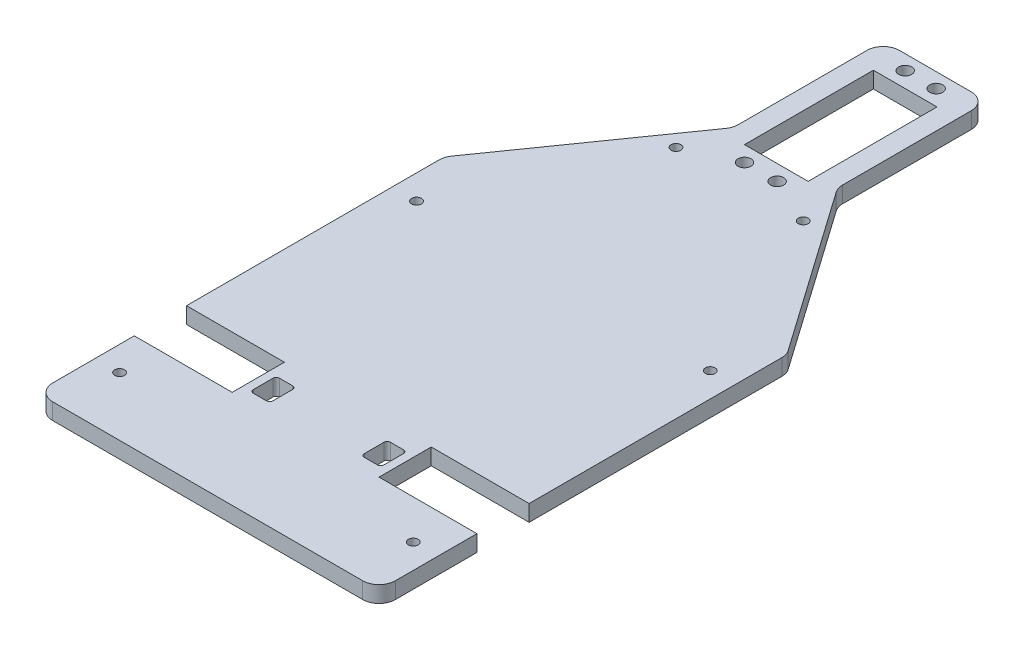
SolidWorks part; units mm, degrees
ref_plane "Front Plane" through (0, 0, 0) normal (0, 0, 1) x (1, 0, 0)
ref_plane "Top Plane" through (0, 0, 0) normal (0, 1, 0) x (1, 0, 0)
ref_plane "Right Plane" through (0, 0, 0) normal (1, 0, 0) x (0, 0, -1)
sketch "Sketch1" plane through (0, 0, 0) normal (0, 1, 0) x (1, 0, 0)
  line L0 (-16, 108) -> (16, 108)
  line L1 (16, 108) -> (16, 62)
  line L2 (16, 62) -> (52.5, 10)
  line L3 (52.5, 10) -> (52.5, -115)
  line L4 (52.5, -115) -> (-52.5, -115)
  line L5 (-52.5, -115) -> (-52.5, 10)
  line L6 (-52.5, 10) -> (-16, 62)
  line L7 (-16, 62) -> (-16, 108)
  dimension "D1" = 52.5
  dimension "D2" = 105
  dimension "D3" = 16
  dimension "D4" = 32
  dimension "D5" = 125
  dimension "D6" = 108
  dimension "D7" = 125
  dimension "D8" = 46
  dimension "D9" = 52
  dimension "D10" = 52
extrude "Boss-Extrude1" add sketch "Sketch1" along normal blind 5
sketch "Sketch2" plane through (0, 5, 0) normal (0, 1, 0) x (1, 0, 0)
  line L5 (-9.75, 59.25) -> (-9.75, 98.75)
  line L16 (52.5, 10) -> (52.5, -115) construction
  line L17 (-52.5, -69) -> (-22.5, -69)
  line L18 (-52.5, -115) -> (-52.5, 10) construction
  line L19 (-22.5, -69) -> (-22.5, -85)
  line L20 (-22.5, -85) -> (-52.5, -85)
  line L21 (-52.5, -85) -> (-52.5, -69)
  line L22 (22.5, -85) -> (22.5, -69)
  line L23 (22.5, -85) -> (52.5, -85)
  line L24 (22.5, -69) -> (52.5, -69)
  line L25 (52.5, -69) -> (52.5, -85)
  line L27 (52.5, -115) -> (-52.5, -115) construction
  line L29 (-20, -82) -> (-14, -82)
  line L30 (-14, -82) -> (-14, -74)
  line L31 (-20, -74) -> (-14, -74)
  line L32 (-20, -82) -> (-20, -74)
  line L33 (14, -74) -> (14, -82)
  line L34 (14, -82) -> (20, -82)
  line L35 (20, -82) -> (20, -74)
  line L36 (20, -74) -> (14, -74)
  line L37 (-16, 108) -> (16, 108) construction
  line L38 (-16, 62) -> (-16, 108) construction
  line L40 (-9.75, 98.75) -> (9.75, 98.75)
  line L41 (9.75, 98.75) -> (9.75, 59.25)
  line L42 (9.75, 59.25) -> (-9.75, 59.25)
  circle A0 centre (-4.75, 103.5) radius 2
  circle A1 centre (4.75, 103.5) radius 2
  circle A2 centre (-5, 54.5006) radius 2
  circle A3 centre (5, 54.5006) radius 2
  circle A6 centre (-19.5, 48) radius 1.5
  circle A7 centre (19.5, 48) radius 1.5
  circle A8 centre (45, -6) radius 1.5
  circle A9 centre (-45, -6) radius 1.5
  circle A10 centre (45, -97) radius 1.5
  circle A11 centre (-45, -97) radius 1.5
  point P18 (0, 0)
  dimension "D5" = 4
  dimension "D8" = 4
  dimension "D11" = 4
  dimension "D14" = 39.5
  dimension "D21" = 91
  dimension "D24" = 16
  dimension "D27" = 3
  dimension "D30" = 3
  dimension "D37" = 3
  dimension "D38" = 3
  dimension "D39" = 3
  dimension "D40" = 3
  dimension "D26" = 4
  dimension "D7" = 4.5
  dimension "D9" = 19.5
  dimension "D10" = 4.5
  dimension "D12" = 6.25
  dimension "D13" = 11
  dimension "D15" = 49
  dimension "D16" = 49
  dimension "D17" = 11
  dimension "D18" = 60
  dimension "D19" = 60
  dimension "D20" = 7.5
  dimension "D22" = 91
  dimension "D23" = 33
  dimension "D25" = 16
  dimension "D28" = 33
  dimension "D33" = 7.5
  dimension "D35" = 7.5
  dimension "D41" = 7.5
  dimension "D42" = 4.75
  dimension "D44" = 5
  dimension "D45" = 5
  dimension "D49" = 30
  dimension "D50" = 16
  dimension "D51" = 30
  dimension "D52" = 16
  dimension "D53" = 30
  dimension "D54" = 30
  dimension "D55" = 8
  dimension "D56" = 6
  dimension "D57" = 2.5
  dimension "D58" = 5
  dimension "D59" = 8
  dimension "D60" = 6
  dimension "D61" = 2.5
  dimension "D62" = 5
extrude "Cut-Extrude1" cut sketch "Sketch2" against normal blind 7
fillet "Fillet1" radius 5 1 edges at (16, 2.5, -108)
fillet "Fillet2" radius 5 1 edges at (-16, 2.5, -108)
fillet "Fillet3" radius 5 1 edges at (52.5, 2.5, -10)
fillet "Fillet4" radius 5 1 edges at (-52.5, 2.5, -10)
fillet "Fillet5" radius 5 1 edges at (52.5, 2.5, 115)
fillet "Fillet6" radius 5 1 edges at (-52.5, 2.5, 115)
fillet "Fillet8" radius 1 1 edges at (20, 2.5, 74)
fillet "Fillet9" radius 1 7 edges at (-20, 2.5, 82) (-20, 2.5, 74) (-14, 2.5, 82) (-14, 2.5, 74) (14, 2.5, 82) (20, 2.5, 82) (14, 2.5, 74)
fillet "Fillet10" radius 5 2 edges at (-16, 2.5, -62) (16, 2.5, -62)
